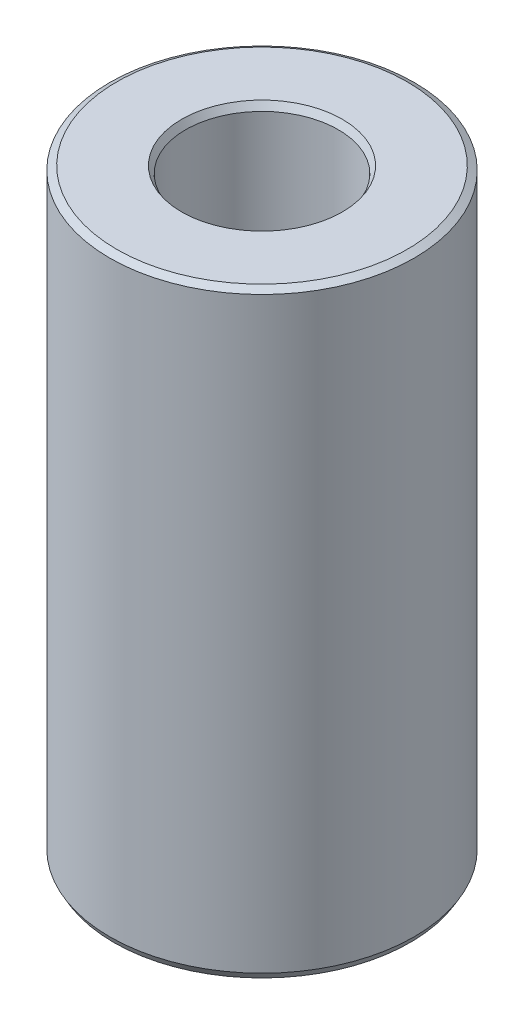
SolidWorks part; units mm, degrees
ref_plane "Front Plane" through (0, 0, 0) normal (0, 0, 1) x (1, 0, 0)
ref_plane "Top Plane" through (0, 0, 0) normal (0, 1, 0) x (1, 0, 0)
ref_plane "Right Plane" through (0, 0, 0) normal (1, 0, 0) x (0, 0, -1)
sketch "Sketch1" plane through (0, 0, 0) normal (0, 1, 0) x (1, 0, 0)
  circle A0 centre (0, 0) radius 12.5
  dimension "SLEEVE_OD" = 25
extrude "Boss-Extrude1" add sketch "Sketch1" along normal blind 49.182
sketch "Sketch2" plane through (0, 0, 0) normal (0, 1, 0) x (1, 0, 0)
  circle A0 centre (0, 0) radius 6.2673
  dimension "BORE_D" = 12.5345
extrude "Cut-Extrude1" cut sketch "Sketch2" along normal through all
chamfer "Chamfer1" distance 0.3315 angle 60 4 edges at (0, 49.182, 6.2673) (0, 0, 6.2673) (0, 0, 12.5) (0, 49.182, 12.5) first distance on face at (0, 49.182, 6.2673) first distance on face at (0, 0, 6.2673) first distance on face at (0, 49.182, 12.5)
